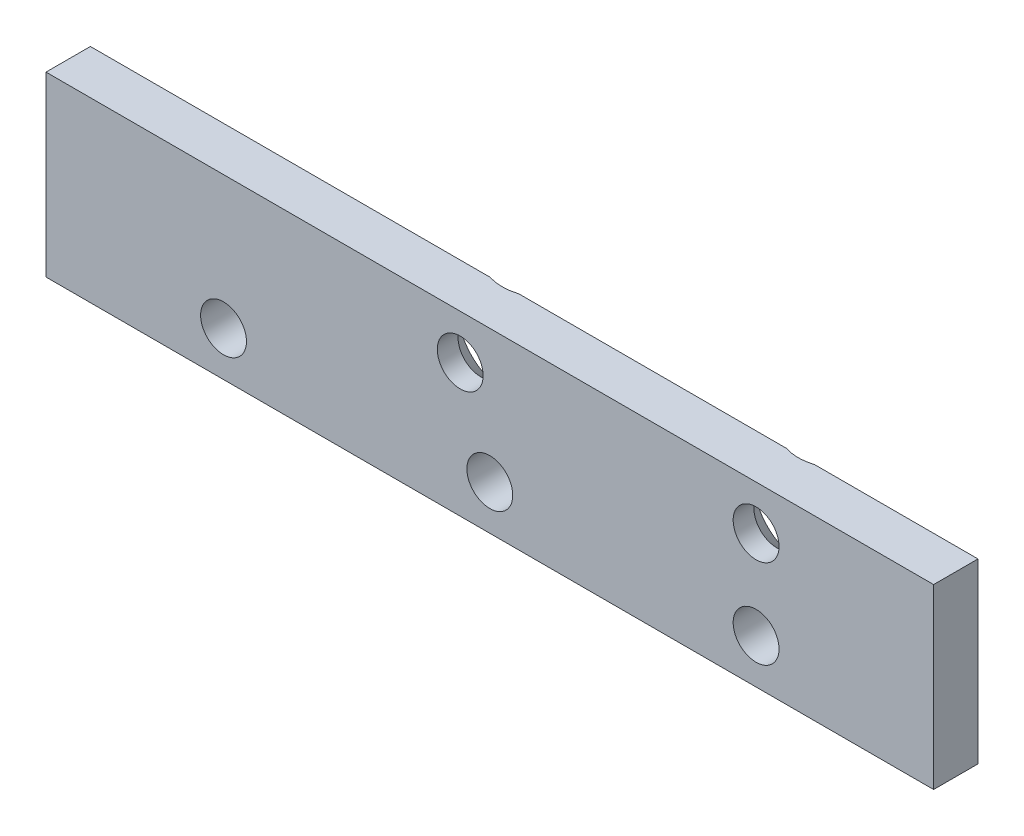
SolidWorks part; units mm, degrees
ref_plane "前视基准面" through (0, 0, 0) normal (0, 0, 1) x (1, 0, 0)
ref_plane "上视基准面" through (0, 0, 0) normal (0, 1, 0) x (1, 0, 0)
ref_plane "右视基准面" through (0, 0, 0) normal (1, 0, 0) x (0, 0, -1)
sketch "草图1" plane through (0, 0, 0) normal (0, 0, 1) x (1, 0, 0)
  line L1 (-30, 6) -> (30, 6)
  line L2 (-30, 6) -> (-30, -6)
  line L3 (-30, -6) -> (30, -6)
  line L4 (30, 6) -> (30, -6)
  line L5 (-30, 6) -> (30, -6) construction
  line L6 (-30, -6) -> (30, 6) construction
  circle A0 centre (18, 3) radius 1.55
  circle A1 centre (-2, 3) radius 1.55
  circle A2 centre (0, -3) radius 1.55
  circle A3 centre (18, -3) radius 1.55
  circle A4 centre (-18, -3) radius 1.55
  point P0 (0, 0)
  dimension "D3" = 3.1
  dimension "D4" = 3.1
  dimension "D6" = 20
  dimension "D9" = 3.1
  dimension "D10" = 3.1
  dimension "D11" = 3.1
  dimension "D12" = 3
  dimension "D13" = 3
  dimension "D14" = 3
  dimension "D1" = 12
  dimension "D2" = 60
  dimension "D5" = 12
  dimension "D7" = 3
  dimension "D8" = 3
  dimension "D15" = 30
  dimension "D16" = 12
  dimension "D17" = 18
extrude "凸台-拉伸1" add sketch "草图1" along normal blind 3
chamfer "倒角1" distance 1.6 angle 45 2 edges at (-0.45, 3, 0) (19.55, 3, 0)
